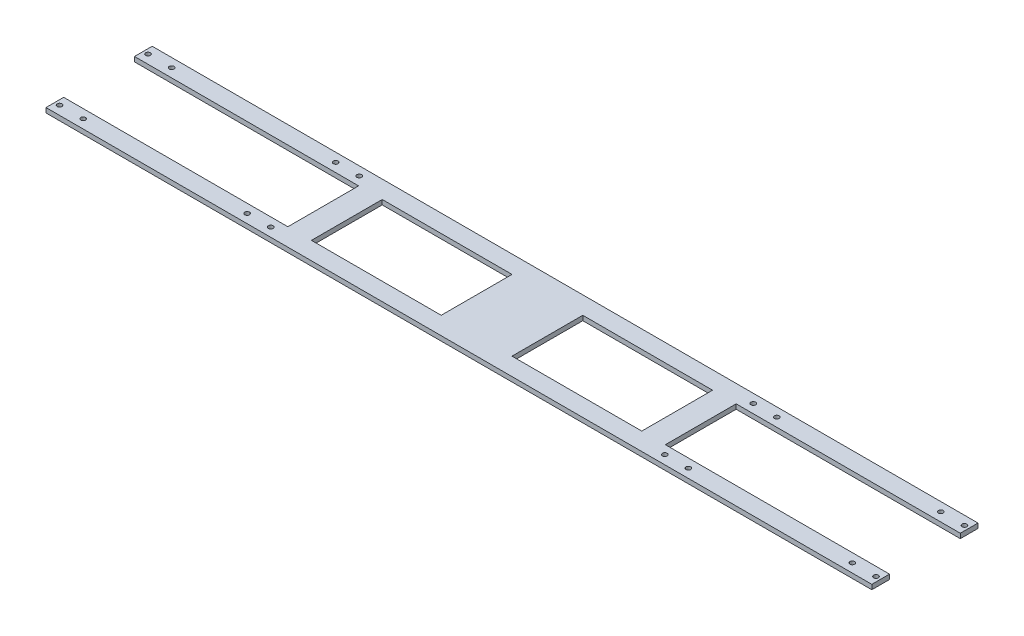
SolidWorks part; units mm, degrees
ref_plane "前视基准面" through (0, 0, 0) normal (0, 0, 1) x (1, 0, 0)
ref_plane "上视基准面" through (0, 0, 0) normal (0, 1, 0) x (1, 0, 0)
ref_plane "右视基准面" through (0, 0, 0) normal (1, 0, 0) x (0, 0, -1)
other "Configuration Table"
sketch "草图1" plane through (0, 0, 0) normal (0, 1, 0) x (1, 0, 0)
  line L1 (-350, -45) -> (350, -45)
  line L2 (-350, -45) -> (-350, 45)
  line L3 (-350, 45) -> (350, 45)
  line L4 (350, -45) -> (350, 45)
  line L5 (-350, -45) -> (350, 45) construction
  line L6 (-350, 45) -> (350, -45) construction
  line L7 (-140, -30) -> (140, -30)
  line L8 (-140, -30) -> (-140, 30)
  line L9 (-140, 30) -> (140, 30)
  line L10 (140, -30) -> (140, 30)
  line L11 (-140, -30) -> (140, 30) construction
  line L12 (-140, 30) -> (140, -30) construction
  point P0 (0, 0)
  point P6 (0, 0)
  dimension "D1" = 700
  dimension "D2" = 90
  dimension "D3" = 60
  dimension "D4" = 280
extrude "凸台-拉伸1" add sketch "草图1" along normal blind 4
sketch "草图2" plane through (0, 4, 0) normal (0, 1, 0) x (1, 0, 0)
  line L0 (-350, 45) -> (-350, -45) construction
  line L1 (-350, -30) -> (-160, -30)
  line L2 (-350, -30) -> (-350, 30)
  line L3 (-350, 30) -> (-160, 30)
  line L4 (-160, -30) -> (-160, 30)
  line L5 (140, 30) -> (-140, 30) construction
  line L6 (-140, -30) -> (140, -30) construction
  line L7 (-140, 30) -> (-140, -30) construction
  dimension "D1" = 20
extrude "切除-拉伸1" cut sketch "草图2" against normal blind 4
mirror "镜向1" about plane through (0, 0, 0) normal (1, 0, 0) of "切除-拉伸1"
sketch "草图4" plane through (0, 4, 0) normal (0, 1, 0) x (1, 0, 0)
  line L0 (350, 45) -> (-350, 45) construction
  line L2 (-350, 45) -> (-350, 30) construction
  circle A0 centre (-187, 37.5) radius 2
  circle A1 centre (-167, 37.5) radius 2
  circle A2 centre (-346, 37.5) radius 2
  circle A3 centre (-326, 37.5) radius 2
  point P8 (0, 0)
  point P9 (-214.6775, 40.4674)
  dimension "D1" = 4
  dimension "D3" = 4
  dimension "D2" = 20
  dimension "D4" = 20
  dimension "D5" = 7.5
  dimension "D6" = 167
  dimension "D7" = 4
extrude "切除-拉伸2" cut sketch "草图4" against normal blind 15
mirror "镜向2" about plane through (0, 0, 0) normal (1, 0, 0) of "切除-拉伸2" second plane through (0, 0, 0) second plane normal (0, 0, 1)
sketch "草图5" plane through (0, 4, 0) normal (0, 1, 0) x (1, 0, 0)
  line L0 (140, 30) -> (-140, 30) construction
  line L1 (-30, -30) -> (30, -30)
  line L2 (-30, -30) -> (-30, 30)
  line L3 (-30, 30) -> (30, 30)
  line L4 (30, -30) -> (30, 30)
  line L5 (-30, -30) -> (30, 30) construction
  line L6 (-30, 30) -> (30, -30) construction
  point P0 (0, 0)
  dimension "D1" = 60
extrude "凸台-拉伸2" add sketch "草图5" against normal blind 4
